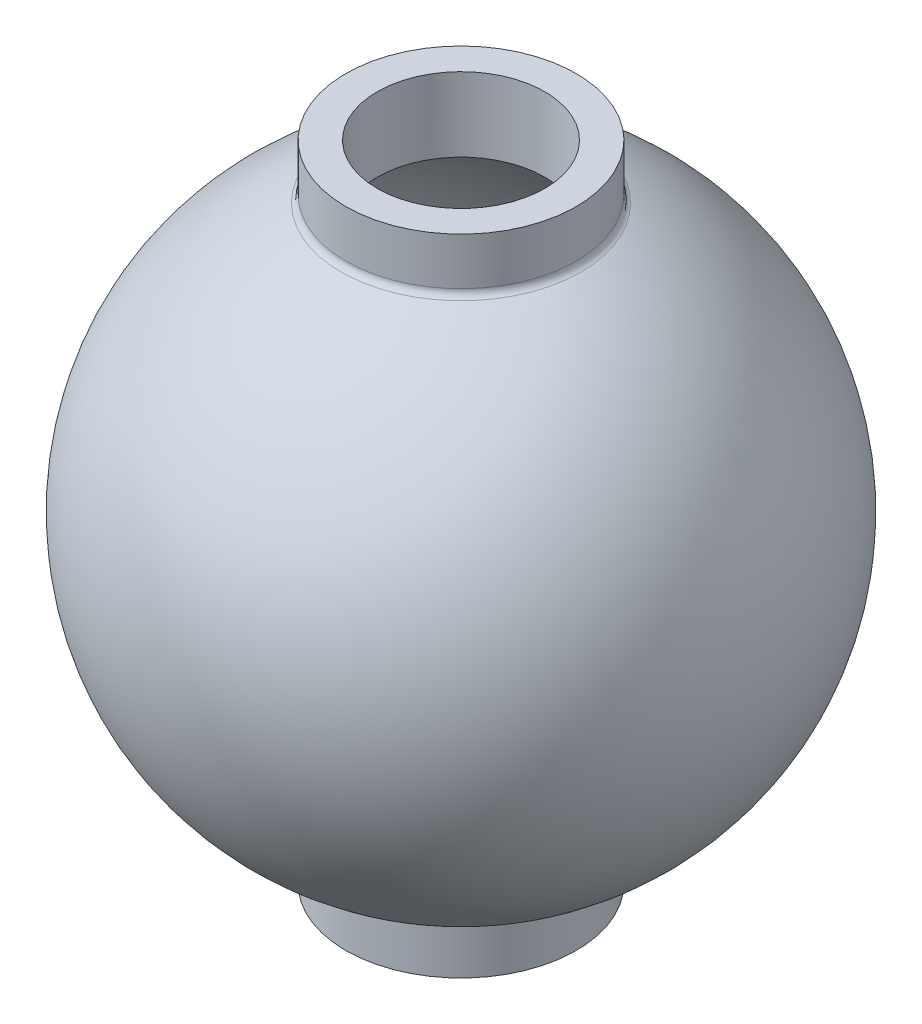
SolidWorks part; units mm, degrees
material "Acrylic (Medium-high impact)"
ref_plane "Front Plane" through (0, 0, 0) normal (0, 0, 1) x (1, 0, 0)
ref_plane "Top Plane" through (0, 0, 0) normal (0, 1, 0) x (1, 0, 0)
ref_plane "Right Plane" through (0, 0, 0) normal (1, 0, 0) x (0, 0, -1)
sketch "Sketch1" plane through (0, 0, 0) normal (0, 0, 1) x (1, 0, 0)
  line L0 (0, 1478.8632) -> (0, -1200.3639) construction
  line L1 (0, 1229.9515) -> (320, 1229.9515)
  line L2 (320, 1229.9515) -> (320, 1073.3126)
  line L3 (320, 1229.9515) -> (440, 1229.9515)
  line L4 (440, 1229.9515) -> (440, 1029.9515)
  line L5 (0, -1229.9515) -> (440, -1229.9515)
  line L6 (440, -1229.9515) -> (440, -1029.9515)
  line L7 (320, -1229.9515) -> (320, -1073.3126)
  arc A0 (0, 1000) -> (0, -1000) centre (0, 0) cw
  arc A1 (0, -1120) -> (0, 1120) centre (0, 0) ccw
  dimension "D1" = 1000
  dimension "D2" = 1120
  dimension "D3" = 320
  dimension "D4" = 120
  dimension "D5" = 200
revolve "Revolve1" add sketch "Sketch1" angle 360 about L0 region at (158.0783, 1083.4851, 0) region at (382.4476, 1140.9935, 0) region at (382.4476, -1140.9935, 0)
sketch "Sketch2" plane through (0, 1229.9515, 0) normal (0, 1, 0) x (1, 0, 0)
  circle A0 centre (0, 0) radius 320
  dimension "D1" = 640
extrude "Cut-Extrude1" cut sketch "Sketch2" against normal blind 1000
fillet "Fillet1" radius 30 2 edges at (0, 1029.9515, 440) (0, -1029.9515, 440)
sketch "Sketch3" plane through (0, 0, 0) normal (0, 1, 0) x (1, 0, 0)
  point P0 (0, 0)
sketch "Sketch4" plane through (0, -1229.9515, 0) normal (0, -1, 0) x (1, 0, 0)
  circle A0 centre (0, 0) radius 300
  circle A1 centre (0, 0) radius 320 construction
  dimension "D1" = 20
extrude "Boss-Extrude1" add sketch "Sketch4" against normal blind 160
equation "\"hatchHoleDiameter\"= 600mm"
equation "\"hullThickness\"= 120mm"
equation "\"gasketHullInterconnectWidth\"= 100mm"
equation "\"collarThickness\"= 20mm"
equation "\"hatchTunnelLength\"=200"
equation "\"oRingDiameter\"=2"
equation "\"boltPatternRadiusInterconnect\"=500"
equation "\"interconnectBoltDiameter\"=30"
equation "\"hatchShaftDiameter\"=20"
equation "\"hatchMinima\"=50"
equation "\"hullDiameter\"=2000"
equation "\"hatchMaxima\"=180"
equation "\"bushingFlatHatch\"=15"
equation "\"hingePivotDiameter\"=20"
equation "\"handleWidth\"=250"
equation "\"handleHeight\"=160"
equation "\"handleThickness\"=25"
equation "\"D2@Sketch1\"=\"hullThickness\"+\"hullDiameter\"/2"
equation "\"D1@Sketch1\"=\"hullDiameter\"/2"
equation "\"D3@Sketch1\"=\"hatchHoleDiameter\"/2 + \"collarThickness\""
equation "\"D4@Sketch1\"=\"hullThickness\""
equation "\"D1@Sketch2\"=\"hatchHoleDiameter\" + 2*\"collarThickness\""
equation "\"D1@Cut-Extrude1\"=\"hullDiameter\"/2"
equation "\"D1@Sketch4\"=\"collarThickness\""
